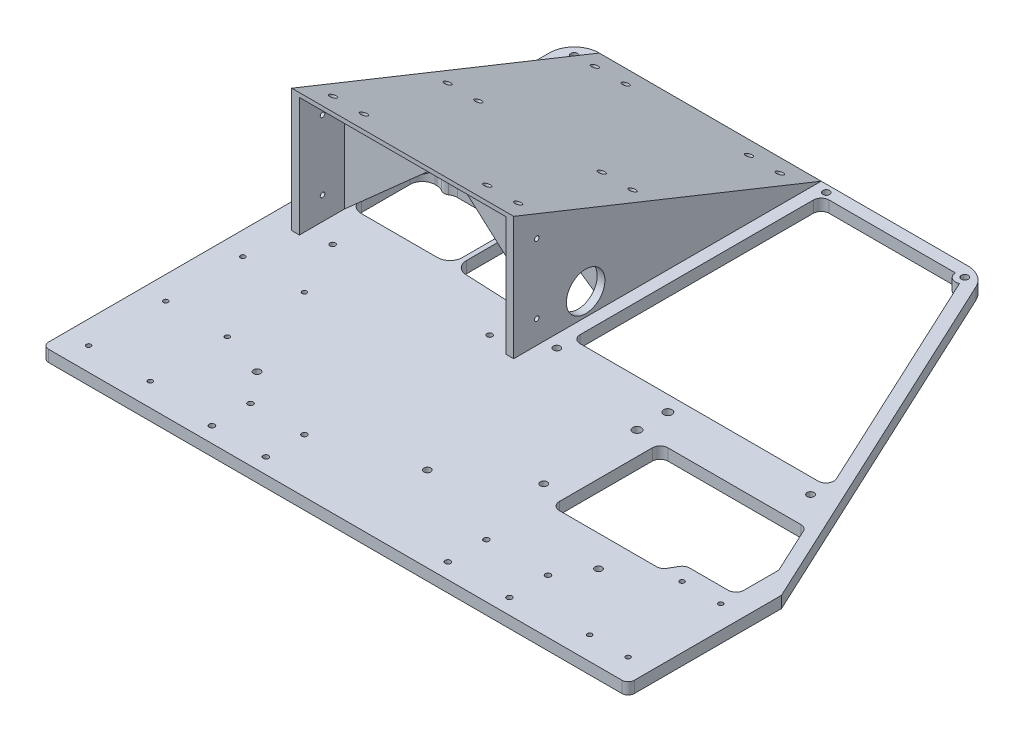
SolidWorks part; units mm, degrees
ref_plane "Front Plane" through (0, 0, 0) normal (0, 0, 1) x (1, 0, 0)
ref_plane "Top Plane" through (0, 0, 0) normal (0, 1, 0) x (1, 0, 0)
ref_plane "Right Plane" through (0, 0, 0) normal (1, 0, 0) x (0, 0, -1)
sketch "Sketch1" plane through (0, 0, 0) normal (0, 1, 0) x (1, 0, 0)
  line L0 (-240.25, 0) -> (139.75, 0) construction
  line L1 (0, -55) -> (0, 290) construction
  line L2 (-236.25, -55) -> (135.75, -55)
  line L3 (139.75, -51) -> (139.75, 44.5)
  line L4 (139.75, 44.5) -> (29.5793, 280.7619)
  line L5 (15.0783, 290) -> (-224.25, 290)
  line L6 (-240.25, 274) -> (-240.25, -51)
  line L7 (0, 90.5) -> (-80, 90.5) construction
  line L8 (-80, 90.5) -> (-80, 290) construction
  line L9 (87.4836, 120.5) -> (-66.9034, 120.5)
  line L10 (-72, 125.5966) -> (-72, 276.9034)
  line L11 (-66.9034, 282) -> (15.0783, 282)
  line L12 (22.3288, 277.3809) -> (92.1026, 127.7505)
  line L13 (22.3288, 277.3809) -> (29.5793, 280.7619) construction
  line L14 (-72, 276.9034) -> (-80, 276.9034) construction
  line L15 (-66.9034, 282) -> (-66.9034, 290) construction
  line L16 (15.0783, 282) -> (15.0783, 290) construction
  line L17 (119.6534, 30) -> (94.75, 30)
  line L19 (15, 25.0966) -> (15, 85.4034)
  line L20 (20.0966, 90.5) -> (106.226, 90.5)
  line L22 (124.75, 35.0966) -> (124.75, 56.6081)
  line L23 (110.845, 87.5573) -> (124.2725, 58.762)
  line L24 (83.0915, 20) -> (20.0966, 20)
  line L26 (87.5052, 22.5483) -> (90.3362, 27.4517)
  arc A0 (135.75, -55) -> (139.75, -51) centre (135.75, -51) ccw
  arc A1 (29.5793, 280.7619) -> (15.0783, 290) centre (15.0783, 274) ccw
  arc A2 (-224.25, 290) -> (-240.25, 274) centre (-224.25, 274) ccw
  arc A3 (-240.25, -51) -> (-236.25, -55) centre (-236.25, -51) ccw
  circle A4 centre (0, 30) radius 2 construction
  circle A5 centre (65.5, 0) radius 2.25
  circle A6 centre (-45.5, 0) radius 2.25
  circle A7 centre (-156, 0) radius 2.25
  circle A8 centre (0, 90.5) radius 2.75
  circle A9 centre (0, 110.5) radius 2.5 construction
  circle A10 centre (0, 110.5) radius 2.75
  circle A11 centre (0, 30) radius 2.25
  arc A12 (-66.9034, 120.5) -> (-72, 125.5966) centre (-66.9034, 125.5966) cw
  arc A13 (-72, 276.9034) -> (-66.9034, 282) centre (-66.9034, 276.9034) cw
  arc A15 (92.1026, 127.7505) -> (87.4836, 120.5) centre (87.4836, 125.5966) cw
  arc A17 (15.0783, 282) -> (22.3288, 277.3809) centre (20.1749, 282) ccw
  arc A18 (20.0966, 20) -> (15, 25.0966) centre (20.0966, 25.0966) cw
  arc A20 (15, 85.4034) -> (20.0966, 90.5) centre (20.0966, 85.4034) cw
  arc A21 (106.226, 90.5) -> (110.845, 87.5573) centre (106.226, 85.4034) cw
  arc A22 (124.75, 35.0966) -> (119.6534, 30) centre (119.6534, 35.0966) cw
  arc A23 (124.75, 56.6081) -> (124.2725, 58.762) centre (119.6534, 56.6081) ccw
  arc A24 (83.0915, 20) -> (87.5052, 22.5483) centre (83.0915, 25.0966) ccw
  arc A25 (90.3362, 27.4517) -> (94.75, 30) centre (94.75, 24.9034) cw
  dimension "D3" = 5
  dimension "D4" = 4
  dimension "D10" = 4
  dimension "D23" = 16
  dimension "D5" = 55
  dimension "D7" = 30
  dimension "D8" = 60.5
  dimension "D9" = 20
  dimension "D11" = 65.5
  dimension "D12" = 45.5
  dimension "D16" = 110.5
  dimension "D18" = 74.25
  dimension "D20" = 179.5
  dimension "D21" = 80
  dimension "D22" = 8
  dimension "D6" = 10
  dimension "D17" = 65
  dimension "D15" = 290
  dimension "D24" = 345
  dimension "D14" = 44.5
  dimension "D13" = 84.25
  dimension "D19" = 380
  dimension "D26" = 30
  dimension "D27" = 15
  dimension "D28" = 15
  dimension "D25" = 20
  dimension "D29" = 30
  dimension "D30" = 30
  dimension "D31" = 120
  dimension "D1" = 0.25
  dimension "D2" = 0.25
extrude "Boss-Extrude1" add sketch "Sketch1" along normal blind 7.5
ref_plane "Extruder Shelf" through (-80, 0, 0) normal (1, 0, 0) x (0, 0, -1)
sketch "Sketch2" plane through (-80, 0, 0) normal (1, 0, 0) x (0, 0, -1)
  line L0 (90.5, 0) -> (90.5, 7.5) construction
  line L1 (90.5, 7.5) -> (90.5, 87.5)
  line L2 (113.25, 7.5) -> (107.75, 7.5) construction
  line L3 (90.5, 7.5) -> (290, 7.5)
  line L4 (290, 7.5) -> (90.5, 87.5)
  line L5 (290, 7.5) -> (290, 0) construction
  dimension "D1" = 80
  dimension "D2" = 214.9424
  dimension "D3" = 68.149
extrude "Boss-Extrude2" add sketch "Sketch2" against normal blind 5
sketch "Sketch3" plane through (0, 106.6423, -42.7638) normal (0, 0.9282, -0.3722) x (1, 0, 0)
  line L0 (-80, 51.4312) -> (-224, 51.4312)
  line L1 (-224, 51.4312) -> (-224, 266.3736)
  line L2 (-224, 266.3736) -> (-80, 266.3736)
  line L3 (-80, 266.3736) -> (-80, 51.4312)
  line L4 (-92, 266.3736) -> (-92, 250.3736) construction
  line L5 (-92, 250.3736) -> (-92, 147.4312) construction
  line L6 (-92, 147.4312) -> (-92, 67.4312) construction
  line L7 (-92, 67.4312) -> (-92, 51.4312) construction
  line L8 (-92, 250.3736) -> (-112, 250.3736) construction
  line L9 (-112, 250.3736) -> (-192, 250.3736) construction
  line L10 (-192, 250.3736) -> (-212, 250.3736) construction
  line L11 (-224, 250.3736) -> (-212, 250.3736) construction
  line L12 (-92, 250.3736) -> (-80, 250.3736) construction
  line L13 (-112, 266.3736) -> (-112, 51.4312) construction
  line L14 (-192, 266.3736) -> (-192, 51.4312) construction
  line L15 (-212, 266.3736) -> (-212, 51.4312) construction
  line L16 (-80, 147.4312) -> (-224, 147.4312) construction
  line L17 (-80, 67.4312) -> (-224, 67.4312) construction
  circle A0 centre (-92, 250.3736) radius 2 construction
  circle A1 centre (-92, 250.3736) radius 2.25
  circle A2 centre (-112, 250.3736) radius 2.25
  circle A3 centre (-192, 250.3736) radius 2.25
  circle A4 centre (-212, 250.3736) radius 2.25
  circle A5 centre (-212, 147.4312) radius 2.25
  circle A6 centre (-192, 147.4312) radius 2.25
  circle A7 centre (-112, 147.4312) radius 2.25
  circle A8 centre (-92, 147.4312) radius 2.25
  circle A9 centre (-92, 67.4312) radius 2.25
  circle A10 centre (-112, 67.4312) radius 2.25
  circle A11 centre (-192, 67.4312) radius 2.25
  circle A12 centre (-212, 67.4312) radius 2.25
  point P46 (-212, 147.4312)
  point P47 (-92, 147.4312)
  point P48 (-112, 147.4312)
  point P49 (-192, 147.4312)
  point P50 (-212, 147.4312)
  point P51 (-192, 147.4312)
  point P52 (-112, 147.4312)
  dimension "D5" = 4
  dimension "D1" = 144
  dimension "D2" = 16
  dimension "D3" = 20
  dimension "D4" = 80
  dimension "D7" = 80
  dimension "D6" = 0.25
extrude "Boss-Extrude3" add sketch "Sketch3" against normal blind 2.5
sketch "Sketch4" plane through (-224, 0, 0) normal (-1, 0, 0) x (0, 0, 1)
  line L0 (-90.5, 87.5) -> (-90.5, 7.5)
  line L1 (-90.5, 7.5) -> (-290, 7.5)
  line L2 (-290, 7.5) -> (-90.5, 87.5)
extrude "Boss-Extrude4" add sketch "Sketch4" against normal blind 5
sketch "Sketch5" plane through (-80, 0, 0) normal (1, 0, 0) x (0, 0, -1)
  line L0 (90.5, 84.8065) -> (90.5, 87.5)
  line L1 (90.5, 87.5) -> (89.5695, 85.1796)
  line L2 (89.5695, 85.1796) -> (90.5, 84.8065) construction
  line L3 (89.5695, 85.1796) -> (90.5, 87.5) construction
  line L4 (89.5695, 85.1796) -> (90.5, 84.8065)
extrude "Cut-Extrude1" cut sketch "Sketch5" against normal up to next
sketch "Sketch6" plane through (-85, 0, 0) normal (-1, 0, 0) x (0, 0, 1)
  line L0 (-90.5, 84.8065) -> (-119.6305, 64.4091)
  line L2 (-90.5, 84.8065) -> (-283.283, 7.5) construction
  line L3 (-122.6305, 71.9221) -> (-151.761, 51.5247)
  line L5 (-154.761, 59.0377) -> (-183.8915, 38.6403)
  line L7 (-186.8915, 46.1532) -> (-216.022, 25.7558)
  line L9 (-219.022, 33.2688) -> (-248.1525, 12.8714)
  line L11 (-251.1525, 20.3844) -> (-269.5534, 7.5)
  line L12 (-90.5, 7.5) -> (-283.283, 7.5) construction
  line L13 (-269.5534, 7.5) -> (-283.283, 7.5)
  line L15 (-90.5, 84.8065) -> (-90.5, 7.5) construction
  line L16 (-283.283, 7.5) -> (-251.1525, 20.3844)
  line L17 (-219.022, 33.2688) -> (-186.8915, 46.1532)
  line L18 (-154.761, 59.0377) -> (-122.6305, 71.9221)
  line L19 (-251.1525, 20.3844) -> (-219.022, 33.2688)
  line L20 (-186.8915, 46.1532) -> (-154.761, 59.0377)
  line L21 (-122.6305, 71.9221) -> (-90.5, 84.8065)
  line L22 (-251.1525, 20.3844) -> (-251.1525, 12.8714)
  line L23 (-251.1525, 12.8714) -> (-248.1525, 12.8714)
  line L24 (-219.022, 33.2688) -> (-219.022, 25.7558)
  line L25 (-219.022, 25.7558) -> (-216.022, 25.7558)
  line L26 (-186.8915, 46.1532) -> (-186.8915, 38.6403)
  line L27 (-186.8915, 38.6403) -> (-183.8915, 38.6403)
  line L28 (-154.761, 59.0377) -> (-154.761, 51.5247)
  line L29 (-154.761, 51.5247) -> (-151.761, 51.5247)
  line L30 (-122.6305, 71.9221) -> (-122.6305, 64.4091)
  line L31 (-122.6305, 64.4091) -> (-119.6305, 64.4091)
  line M19 (-90.5, 84.8065) -> (-283.283, 7.5)
  line M20 (-283.283, 7.5) -> (-90.5, 7.5)
  dimension "D1" = 55
  dimension "D2" = 3
extrude "Boss-Extrude5" add sketch "Sketch6" along normal up to surface (134 mm away) contours L30 L31 L0 M19 | L28 L29 L3 M19 | L26 L27 L5 M19 | L24 L25 L7 M19 | L22 L23 L9 M19 | L11 M19 M20 region at (-85, 11.7948, -267.9963) region at (-85, 21.6684, -240.2401) region at (-85, 34.5529, -208.1096) region at (-85, 47.4373, -175.9791) region at (-85, 60.3217, -143.8486) region at (-85, 73.2061, -111.7181) up to face at (-219, 33.2688, -154.761)
ref_plane "Plane2" through (0, 0, -248.1525) normal (0, 0, 1) x (1, 0, 0)
sketch "Sketch7" plane through (0, 0, -248.1525) normal (0, 0, 1) x (1, 0, 0)
  line L0 (-85, 12.8714) -> (-94.3036, 7.5)
  line L2 (-219, 7.5) -> (-85, 7.5) construction
  line L3 (-85, 12.8714) -> (-106.6072, 12.8714)
  line L4 (-219, 12.8714) -> (-85, 12.8714) construction
  line L5 (-106.6072, 12.8714) -> (-97.3036, 7.5)
  line L6 (-97.3036, 7.5) -> (-94.3036, 7.5)
  line L7 (-106.6072, 12.8714) -> (-112.6072, 12.8714) construction
  line L8 (-112.6072, 12.8714) -> (-121.9108, 7.5)
  line L9 (-121.9108, 7.5) -> (-124.9108, 7.5)
  line L10 (-124.9108, 7.5) -> (-134.2143, 12.8714)
  line L11 (-134.2143, 12.8714) -> (-112.6072, 12.8714)
  line L12 (-219, 12.8714) -> (-209.6964, 7.5)
  line L13 (-209.6964, 7.5) -> (-206.6964, 7.5)
  line L14 (-206.6964, 7.5) -> (-197.3928, 12.8714)
  line L15 (-197.3928, 12.8714) -> (-219, 12.8714)
  line L16 (-197.3928, 12.8714) -> (-191.3928, 12.8714) construction
  line L17 (-191.3928, 12.8714) -> (-182.0892, 7.5)
  line L18 (-182.0892, 7.5) -> (-179.0892, 7.5)
  line L19 (-179.0892, 7.5) -> (-169.7857, 12.8714)
  line L20 (-169.7857, 12.8714) -> (-191.3928, 12.8714)
  line L21 (-162.8036, 12.8714) -> (-153.5, 7.5)
  line L22 (-153.5, 7.5) -> (-150.5, 7.5)
  line L23 (-150.5, 7.5) -> (-141.1964, 12.8714)
  line L24 (-141.1964, 12.8714) -> (-162.8036, 12.8714)
  point P26 (-152, 7.5)
  point P29 (-152, 7.5)
  dimension "D1" = 30
  dimension "D2" = 30
  dimension "D3" = 3
  dimension "D4" = 6
extrude "Boss-Extrude6" add sketch "Sketch7" against normal up to surface (3 mm away) up to face at (-152, 16.6279, -251.1525)
ref_plane "Plane3" through (0, 0, -216.022) normal (0, 0, 1) x (1, 0, 0)
sketch "Sketch8" plane through (0, 0, -216.022) normal (0, 0, 1) x (1, 0, 0)
  line L0 (-85, 25.7558) -> (-85, 7.5)
  line L1 (-85, 7.5) -> (-116.62, 25.7558)
  line L2 (-219, 25.7558) -> (-85, 25.7558) construction
  line L3 (-116.62, 25.7558) -> (-85, 25.7558)
  line L4 (-219, 25.7558) -> (-187.38, 25.7558)
  line L5 (-187.38, 25.7558) -> (-219, 7.5)
  line L6 (-219, 7.5) -> (-219, 25.7558)
  line L7 (-85, 7.5) -> (-219, 7.5) construction
  line L8 (-116.62, 25.7558) -> (-118.88, 25.7558) construction
  line L9 (-118.88, 25.7558) -> (-150.5, 7.5)
  line L10 (-150.5, 7.5) -> (-153.5, 7.5)
  line L11 (-153.5, 7.5) -> (-185.12, 25.7558)
  line L12 (-187.38, 25.7558) -> (-185.12, 25.7558) construction
  line L13 (-185.12, 25.7558) -> (-118.88, 25.7558)
  dimension "D1" = 60
  dimension "D2" = 60
  dimension "D3" = 3
extrude "Boss-Extrude7" add sketch "Sketch8" against normal up to surface (3 mm away) up to face at (-152, 29.5123, -219.022)
ref_plane "Plane4" through (0, 0, -183.8915) normal (0, 0, 1) x (1, 0, 0)
sketch "Sketch9" plane through (0, 0, -183.8915) normal (0, 0, 1) x (1, 0, 0)
  line L0 (-85, 38.6403) -> (-85, 7.5)
  line L1 (-85, 7.5) -> (-138.9365, 38.6403)
  line L2 (-219, 38.6403) -> (-85, 38.6403) construction
  line L3 (-138.9365, 38.6403) -> (-85, 38.6403)
  line L4 (-219, 38.6403) -> (-165.0635, 38.6403)
  line L5 (-165.0635, 38.6403) -> (-219, 7.5)
  line L6 (-219, 7.5) -> (-219, 38.6403)
  line L7 (-165.0635, 38.6403) -> (-159.0635, 38.6403) construction
  line L8 (-159.0635, 38.6403) -> (-144.9365, 38.6403)
  line L9 (-144.9365, 38.6403) -> (-138.9365, 38.6403) construction
  line L10 (-159.0635, 38.6403) -> (-154, 7.5)
  line L14 (-150, 7.5) -> (-144.9365, 38.6403)
  line L15 (-219, 7.5) -> (-85, 7.5) construction
  line L16 (-154, 7.5) -> (-150, 7.5)
  dimension "D1" = 60
  dimension "D2" = 60
  dimension "D3" = 6
  dimension "D4" = 4
extrude "Boss-Extrude8" add sketch "Sketch9" against normal up to surface (3 mm away) up to face at (-152, 42.3967, -186.8915)
ref_plane "Plane5" through (0, 0, -151.761) normal (0, 0, 1) x (1, 0, 0)
sketch "Sketch10" plane through (0, 0, -151.761) normal (0, 0, 1) x (1, 0, 0)
  line L0 (-85, 51.5247) -> (-85, 7.5)
  line L1 (-85, 7.5) -> (-149, 51.5247)
  line L2 (-219, 51.5247) -> (-85, 51.5247) construction
  line L3 (-149, 51.5247) -> (-85, 51.5247)
  line L4 (-219, 51.5247) -> (-219, 7.5)
  line L5 (-219, 7.5) -> (-155, 51.5247)
  line L6 (-155, 51.5247) -> (-219, 51.5247)
  line L7 (-155, 51.5247) -> (-149, 51.5247) construction
  dimension "D1" = 6
  dimension "D2" = 55.476
extrude "Boss-Extrude9" add sketch "Sketch10" against normal up to surface (3 mm away) up to face at (-152, 55.2812, -154.761)
ref_plane "Plane6" through (0, 0, -119.6305) normal (0, 0, 1) x (1, 0, 0)
sketch "Sketch11" plane through (0, 0, -119.6305) normal (0, 0, 1) x (1, 0, 0)
  line L0 (-85, 64.4091) -> (-85, 7.5)
  line L1 (-85, 7.5) -> (-149, 64.4091)
  line L2 (-219, 64.4091) -> (-85, 64.4091) construction
  line L3 (-149, 64.4091) -> (-85, 64.4091)
  line L4 (-219, 64.4091) -> (-219, 7.5)
  line L5 (-219, 7.5) -> (-155, 64.4091)
  line L6 (-155, 64.4091) -> (-219, 64.4091)
  line L7 (-149, 64.4091) -> (-155, 64.4091) construction
  dimension "D1" = 6
extrude "Boss-Extrude10" add sketch "Sketch11" against normal up to surface (3 mm away) up to face at (-152, 68.1656, -122.6305)
sketch "Sketch12" plane through (0, 7.5, 0) normal (0, 1, 0) x (1, 0, 0)
  line L0 (-219, 122.6305) -> (-153.5, 122.6305)
  line L1 (-153.5, 122.6305) -> (-153.5, 248.1525)
  line L2 (-219, 122.6305) -> (-219, 248.1525)
  line L3 (-219, 248.1525) -> (-153.5, 248.1525)
  line L4 (-153.5, 122.6305) -> (-150.5, 122.6305) construction
  line L5 (-150.5, 122.6305) -> (-85, 119.6305)
  line L6 (-150.5, 248.1525) -> (-150.5, 122.6305)
  line L7 (-150.5, 248.1525) -> (-85, 248.1525)
  line L8 (-85, 248.1525) -> (-85, 119.6305)
extrude "Cut-Extrude2" cut sketch "Sketch12" against normal up to next
chamfer "Chamfer1" distance 1 angle 45 2 edges at (-150.5, 7.5, -185.3915) (-153.5, 7.5, -185.3915)
fillet "Fillet1" radius 8 8 edges at (-85, 3.75, -119.6305) (-219, 3.75, -122.6305) (-219, 3.75, -248.1525) (-150.5, 3.75, -248.1525) (-85, 3.75, -248.1525) (-153.5, 3.75, -248.1525) (-150.5, 3.75, -122.6305) (-153.5, 3.75, -122.6305) tangent propagation no
sketch "Sketch13" plane through (0, 7.5, 0) normal (0, 1, 0) x (1, 0, 0)
  line L0 (-152, 176.3) -> (-152, 92) construction
  line L1 (-206.835, 92) -> (-97.165, 92) construction
  line L2 (-206.835, 92) -> (-206.835, 176.3) construction
  line L3 (-206.835, 176.3) -> (-97.165, 176.3) construction
  line L4 (-97.165, 92) -> (-97.165, 176.3) construction
  line L5 (-202.925, 96) -> (-101.075, 96) construction
  line L6 (-202.925, 96) -> (-202.925, 172.3) construction
  line L7 (-202.925, 172.3) -> (-101.075, 172.3) construction
  line L8 (-101.075, 96) -> (-101.075, 172.3) construction
  line L9 (-206.835, 134.15) -> (-97.165, 134.15) construction
  line L10 (-153.5, 183.8915) -> (-150.5, 183.8915) construction
  line L11 (-153.5, 130.6305) -> (-153.5, 183.8915) construction
  line L12 (-150.5, 183.8915) -> (-150.5, 130.2725) construction
  line L13 (-152, 183.8915) -> (-152, 176.3) construction
  line L14 (-153.5, 183.8915) -> (-150.5, 183.8915) construction
  line L15 (-219, 90.5) -> (-85, 90.5) construction
  line L16 (-97.165, 92) -> (-97.165, 90.5) construction
  circle A0 centre (-202.925, 96) radius 1.75
  circle A1 centre (-202.925, 172.3) radius 1.75
  circle A2 centre (-101.075, 172.3) radius 1.75
  circle A3 centre (-101.075, 96) radius 1.5 construction
  circle A4 centre (-101.075, 96) radius 1.75
  point P10 (-152, 96)
  point P13 (-202.925, 134.15)
  dimension "D6" = 0.25
  dimension "D7" = 3
  dimension "D1" = 109.67
  dimension "D2" = 101.85
  dimension "D3" = 84.3
  dimension "D4" = 76.3
  dimension "D5" = 1.5
sketch "Sketch14" plane through (0, 7.5, 0) normal (0, 1, 0) x (1, 0, 0)
  line L0 (-85, 128.0053) -> (-85, 174.3) construction
  line L1 (-85, 128.0053) -> (-85, 122.6305) construction
  line L2 (-97.6109, 174.3) -> (-85, 174.3)
  line L3 (-85, 174.3) -> (-85, 170.3)
  line L4 (-85, 170.3) -> (-97.6109, 170.3)
  line L5 (-85, 172.3) -> (-101.075, 172.3) construction
  line L6 (-104.5391, 174.3) -> (-199.4609, 174.3)
  line L7 (-199.4609, 170.3) -> (-104.5391, 170.3)
  line L8 (-219, 130.6305) -> (-219, 174.3) construction
  line L9 (-219, 122.6305) -> (-219, 130.6305) construction
  line L10 (-219, 174.3) -> (-206.3891, 174.3)
  line L11 (-206.3891, 170.3) -> (-219, 170.3)
  line L12 (-219, 170.3) -> (-219, 174.3)
  circle A0 centre (-101.075, 172.3) radius 1.75 construction
  circle A1 centre (-202.925, 172.3) radius 1.75 construction
  circle A2 centre (-101.075, 172.3) radius 1.75
  circle A3 centre (-202.925, 172.3) radius 1.75
  arc A4 (-206.3891, 174.3) -> (-199.4609, 174.3) centre (-202.925, 172.3) cw
  arc A5 (-199.4609, 170.3) -> (-206.3891, 170.3) centre (-202.925, 172.3) cw
  arc A6 (-97.6109, 174.3) -> (-104.5391, 174.3) centre (-101.075, 172.3) ccw
  arc A7 (-97.6109, 170.3) -> (-104.5391, 170.3) centre (-101.075, 172.3) cw
  dimension "D1" = 8
  dimension "D2" = 4
extrude "Boss-Extrude11" add sketch "Sketch14" against normal up to surface (7.5 mm away) up to face at (-186.25, 0, -185.3915)
fillet "Fillet2" radius 8 16 edges at (-97.6109, 3.75, -174.3) (-104.5391, 3.75, -174.3) (-199.4609, 3.75, -174.3) (-206.3891, 3.75, -174.3) (-199.4609, 3.75, -170.3) (-206.3891, 3.75, -170.3) (-97.6109, 3.75, -170.3) (-104.5391, 3.75, -170.3) (-85, 3.75, -174.3) (-153.5, 3.75, -174.3) (-150.5, 3.75, -174.3) (-219, 3.75, -174.3) (-219, 3.75, -170.3) (-150.5, 3.75, -170.3) (-85, 3.75, -170.3) (-153.5, 3.75, -170.3)
extrude "Cut-Extrude3" cut sketch "Sketch13" against normal through all contours A0 | A4 region at (-202.925, 7.5, -96) region at (-101.075, 7.5, -96)
sketch "Sketch15" plane through (-80, 0, 0) normal (1, 0, 0) x (0, 0, -1)
  line L0 (90.5, 22.5) -> (105.5, 22.5) construction
  line L1 (90.5, 87.5) -> (90.5, 7.5) construction
  line L2 (105.5, 7.5) -> (105.5, 81.485) construction
  line L3 (90.5, 7.5) -> (290, 7.5) construction
  line L4 (290, 7.5) -> (90.5, 87.5) construction
  line L5 (105.5, 67.5) -> (90.5, 67.5) construction
  circle A0 centre (105.5, 22.5) radius 1.5
  circle A1 centre (105.5, 67.5) radius 1.25 construction
  circle A2 centre (105.5, 67.5) radius 1.5
  dimension "D5" = 2.5
  dimension "D1" = 15
  dimension "D2" = 45
  dimension "D3" = 15
extrude "Cut-Extrude5" cut sketch "Sketch15" against normal through all
sketch "Sketch16" plane through (0, 7.5, 0) normal (0, 1, 0) x (1, 0, 0)
  line L0 (-235.5637, 285.3137) -> (-217.7647, 303.1127) construction
  line L1 (-235.5637, 285.3137) -> (-230.7739, 280.5239) construction
  line L2 (-230.7739, 280.5239) -> (-224, 280.5239) construction
  line L3 (-224, 290) -> (-224, 90.5) construction
  line L4 (-72, 276.9034) -> (-72, 285.2861) construction
  line L5 (-72, 276.9034) -> (-72, 125.5966) construction
  line L6 (-72, 285.2861) -> (-72, 290) construction
  line L7 (15.0783, 290) -> (-80, 290) construction
  line L8 (-72, 285.2861) -> (-69.5511, 281.2583) construction
  line L9 (-69.5511, 281.2583) -> (-64.5816, 284.2797) construction
  line L10 (17.4365, 277.7016) -> (23.6751, 287.4943) construction
  line L11 (0, 110.5) -> (108.9737, 110.5) construction
  line L12 (139.75, 44.5) -> (29.5793, 280.7619) construction
  line L13 (92.5802, 110.5) -> (92.5802, 125.5966) construction
  line L14 (0, 110.5) -> (-80, 110.5) construction
  line L15 (-80, 90.5) -> (-80, 290) construction
  line L16 (-72, 110.5) -> (-72, 125.5966) construction
  arc A0 (-224.25, 290) -> (-240.25, 274) centre (-224.25, 274) ccw construction
  circle A2 centre (-230.7739, 280.5239) radius 2 construction
  circle A3 centre (-230.7739, 280.5239) radius 2.25
  arc A4 (-66.9034, 282) -> (-72, 276.9034) centre (-66.9034, 276.9034) ccw construction
  circle A5 centre (-72, 285.2861) radius 2.25
  circle A8 centre (20.5558, 282.5979) radius 2.25
  arc A9 (15.0783, 282) -> (22.3288, 277.3809) centre (20.1749, 282) ccw construction
  arc A10 (29.5793, 280.7619) -> (15.0783, 290) centre (15.0783, 274) ccw construction
  arc A11 (87.4836, 120.5) -> (92.1026, 127.7505) centre (87.4836, 125.5966) ccw construction
  circle A12 centre (92.5802, 110.5) radius 2.25
  circle A13 centre (-72, 110.5) radius 2.25
  dimension "D1" = 0.25
  dimension "D2" = 4
extrude "Cut-Extrude6" cut sketch "Sketch16" against normal through all
sketch "Sketch17" plane through (-85, 0, 0) normal (-1, 0, 0) x (0, 0, 1)
  line L0 (-151.761, 7.5) -> (-122.6305, 7.5) construction
  line L1 (-137.1958, 7.5) -> (-137.1958, 9.5) construction
  circle A0 centre (-137.1958, 22) radius 12.5
  dimension "D1" = 25
  dimension "D2" = 2
extrude "Cut-Extrude7" cut sketch "Sketch17" against normal up to next
sketch "Sketch18" plane through (0, 7.5, 0) normal (0, 1, 0) x (1, 0, 0)
  line L0 (-240.25, -40) -> (-225.25, -40) construction
  line L1 (-225.25, -40) -> (-185.25, -40) construction
  line L2 (-225.25, -40) -> (-225.25, 10) construction
  line L3 (-225.25, 10) -> (-185.25, 10) construction
  line L4 (-185.25, -40) -> (-185.25, 10) construction
  line L5 (-240.25, 274) -> (-240.25, -51) construction
  line L6 (-225.25, -40) -> (-225.25, -55) construction
  line L7 (-236.25, -55) -> (135.75, -55) construction
  line L8 (124.75, -55) -> (124.75, -40) construction
  line L9 (124.75, -40) -> (139.75, -40) construction
  line L10 (139.75, -51) -> (139.75, 44.5) construction
  line L11 (-140.25, -45) -> (-140.25, -55)
  line L12 (124.75, -40) -> (99.75, -40) construction
  line L13 (124.75, -40) -> (124.75, 20) construction
  line L14 (124.75, 20) -> (99.75, 20) construction
  line L15 (99.75, -40) -> (99.75, 20) construction
  line L16 (-140.25, -45) -> (-105.25, -45) construction
  line L17 (-140.25, -45) -> (-140.25, -20) construction
  line L18 (-140.25, -20) -> (-105.25, -20) construction
  line L19 (-105.25, -45) -> (-105.25, -20) construction
  line L20 (12.75, -45) -> (52.75, -45) construction
  line L21 (12.75, -45) -> (12.75, -20) construction
  line L22 (12.75, -20) -> (52.75, -20) construction
  line L23 (52.75, -45) -> (52.75, -20) construction
  line L26 (-225.25, 10) -> (-185.25, 10) construction
  line L27 (-225.25, 10) -> (-225.25, 60) construction
  line L28 (-225.25, 60) -> (-185.25, 60) construction
  line L29 (-185.25, 10) -> (-185.25, 60) construction
  circle A0 centre (-185.25, 10) radius 1.5
  circle A1 centre (-225.25, 10) radius 1.5
  circle A2 centre (-185.25, -40) radius 1.5
  circle A3 centre (-225.25, -40) radius 1.25 construction
  circle A4 centre (-225.25, -40) radius 1.5
  circle A5 centre (124.75, -40) radius 1.5
  circle A6 centre (99.75, -40) radius 1.5
  circle A7 centre (99.75, 20) radius 1.5
  circle A8 centre (124.75, 20) radius 1.5
  circle A9 centre (-140.25, -20) radius 1.75
  circle A10 centre (-105.25, -20) radius 1.75
  circle A11 centre (-105.25, -45) radius 1.75
  circle A12 centre (12.75, -45) radius 1.75
  circle A13 centre (12.75, -20) radius 1.75
  circle A14 centre (52.75, -45) radius 1.75
  circle A15 centre (52.75, -20) radius 1.75
  circle A16 centre (-140.25, -45) radius 1.5 construction
  circle A17 centre (-140.25, -45) radius 1.75
  circle A18 centre (-225.25, 60) radius 1.5
  circle A19 centre (-185.25, 60) radius 1.5
  dimension "D5" = 2.5
  dimension "D1" = 15
  dimension "D15" = 3
  dimension "D2" = 50
  dimension "D3" = 40
  dimension "D6" = 60
  dimension "D7" = 25
  dimension "D8" = 10
  dimension "D9" = 25
  dimension "D10" = 45
  dimension "D11" = 35
  dimension "D12" = 40
  dimension "D13" = 118
  dimension "D14" = 0.25
extrude "Cut-Extrude8" cut sketch "Sketch18" against normal up to next contours A4 | A2 | A1 | A0 | A17 | A9 | A10 | A11 | A12 | A13 | A15 | A14 | A7 | A8 | A6 | A5 | A19 | A18 region at (-185.25, 7.5, -10) region at (-225.25, 7.5, -10) region at (-185.25, 7.5, 40) region at (-225.25, 7.5, 40) region at (124.75, 7.5, 40) region at (99.75, 7.5, 40) region at (99.75, 7.5, -20) region at (124.75, 7.5, -20) region at (-140.25, 7.5, 20) region at (-105.25, 7.5, 20) region at (-105.25, 7.5, 45) region at (12.75, 7.5, 45) region at (12.75, 7.5, 20) region at (52.75, 7.5, 45) region at (52.75, 7.5, 20) region at (-139.0476, 7.5, 46.2024) region at (-225.25, 7.5, -60) region at (-185.25, 7.5, -60)
sketch "Sketch19" plane through (0, 106.6423, -42.7638) normal (0, 0.9282, -0.3722) x (1, 0, 0)
  circle A0 centre (-92, 250.3736) radius 2.25 construction
  circle A1 centre (-112, 250.3736) radius 2.25 construction
  circle A2 centre (-92, 147.4312) radius 2.25 construction
  circle A3 centre (-112, 147.4312) radius 2.25 construction
  circle A4 centre (-92, 67.4312) radius 2.25 construction
  circle A5 centre (-112, 67.4312) radius 2.25 construction
  circle A6 centre (-192, 67.4312) radius 2.25 construction
  circle A7 centre (-212, 67.4312) radius 2.25 construction
  circle A8 centre (-192, 147.4312) radius 2.25 construction
  circle A9 centre (-212, 147.4312) radius 2.25 construction
  circle A10 centre (-192, 250.3736) radius 2.25 construction
  circle A11 centre (-212, 250.3736) radius 2.25 construction
  circle A12 centre (-92, 250.3736) radius 2.25
  circle A13 centre (-112, 250.3736) radius 2.25
  circle A14 centre (-92, 147.4312) radius 2.25
  circle A15 centre (-112, 147.4312) radius 2.25
  circle A16 centre (-92, 67.4312) radius 2.25
  circle A17 centre (-112, 67.4312) radius 2.25
  circle A18 centre (-192, 67.4312) radius 2.25
  circle A19 centre (-212, 67.4312) radius 2.25
  circle A20 centre (-192, 147.4312) radius 2.25
  circle A21 centre (-212, 147.4312) radius 2.25
  circle A22 centre (-192, 250.3736) radius 2.25
  circle A23 centre (-212, 250.3736) radius 2.25
extrude "Cut-Extrude9" cut sketch "Sketch19" against normal up to next
ref_plane "Plane7" through (0, 104.3219, -41.8334) normal (0, 0.9282, -0.3722) x (1, 0, 0)
sketch "Sketch20" plane through (0, 104.3219, -41.8334) normal (0, 0.9282, -0.3722) x (1, 0, 0)
  circle A0 centre (-212, 250.3736) radius 2.25 construction
  circle A1 centre (-192, 250.3736) radius 2.25 construction
  circle A2 centre (-212, 147.4312) radius 2.25 construction
  circle A3 centre (-192, 147.4312) radius 2.25 construction
  circle A4 centre (-212, 67.4312) radius 2.25 construction
  circle A5 centre (-192, 67.4312) radius 2.25 construction
  circle A6 centre (-112, 67.4312) radius 2.25 construction
  circle A7 centre (-92, 67.4312) radius 2.25 construction
  circle A8 centre (-112, 147.4312) radius 2.25 construction
  circle A9 centre (-92, 147.4312) radius 2.25 construction
  circle A10 centre (-112, 250.3736) radius 2.25 construction
  circle A11 centre (-92, 250.3736) radius 2.25 construction
  circle A12 centre (-212, 250.3736) radius 2.25 construction
  circle A13 centre (-192, 250.3736) radius 2.25 construction
  circle A14 centre (-212, 147.4312) radius 2.25 construction
  circle A15 centre (-192, 147.4312) radius 2.25 construction
  circle A16 centre (-212, 67.4312) radius 2.25 construction
  circle A17 centre (-192, 67.4312) radius 2.25 construction
  circle A18 centre (-112, 67.4312) radius 2.25 construction
  circle A19 centre (-92, 67.4312) radius 2.25 construction
  circle A20 centre (-112, 147.4312) radius 2.25 construction
  circle A21 centre (-92, 147.4312) radius 2.25 construction
  circle A22 centre (-112, 250.3736) radius 2.25 construction
  circle A23 centre (-92, 250.3736) radius 2.25 construction
  circle A24 centre (-212, 250.3736) radius 4.75
  circle A25 centre (-192, 250.3736) radius 4.75
  circle A26 centre (-112, 250.3736) radius 4.75
  circle A27 centre (-92, 250.3736) radius 4.5 construction
  circle A28 centre (-212, 147.4312) radius 4.75
  circle A29 centre (-192, 147.4312) radius 4.75
  circle A30 centre (-112, 147.4312) radius 4.75
  circle A31 centre (-92, 147.4312) radius 4.75
  circle A32 centre (-212, 67.4312) radius 4.75
  circle A33 centre (-192, 67.4312) radius 4.75
  circle A34 centre (-112, 67.4312) radius 4.75
  circle A35 centre (-92, 67.4312) radius 4.75
  circle A36 centre (-92, 250.3736) radius 4.75
  dimension "D1" = 0.25
  dimension "D2" = 9
extrude "Cut-Extrude10" cut sketch "Sketch20" against normal up to next
equation "\"Tolerance\"=0.25"
equation "\"D1@Sketch1\"=\"Tolerance\""
equation "\"D2@Sketch1\"=\"Tolerance\""
equation "\"D6@Sketch3\"=\"Tolerance\""
equation "\"D6@Sketch13\"=\"Tolerance\""
equation "\"D4@Sketch15\"=\"Tolerance\""
equation "\"D1@Sketch16\"=\"Tolerance\""
equation "\"D4@Sketch18\"=\"Tolerance\""
equation "\"D14@Sketch18\"=\"Tolerance\""
equation "\"D1@Sketch20\"=\"Tolerance\""
